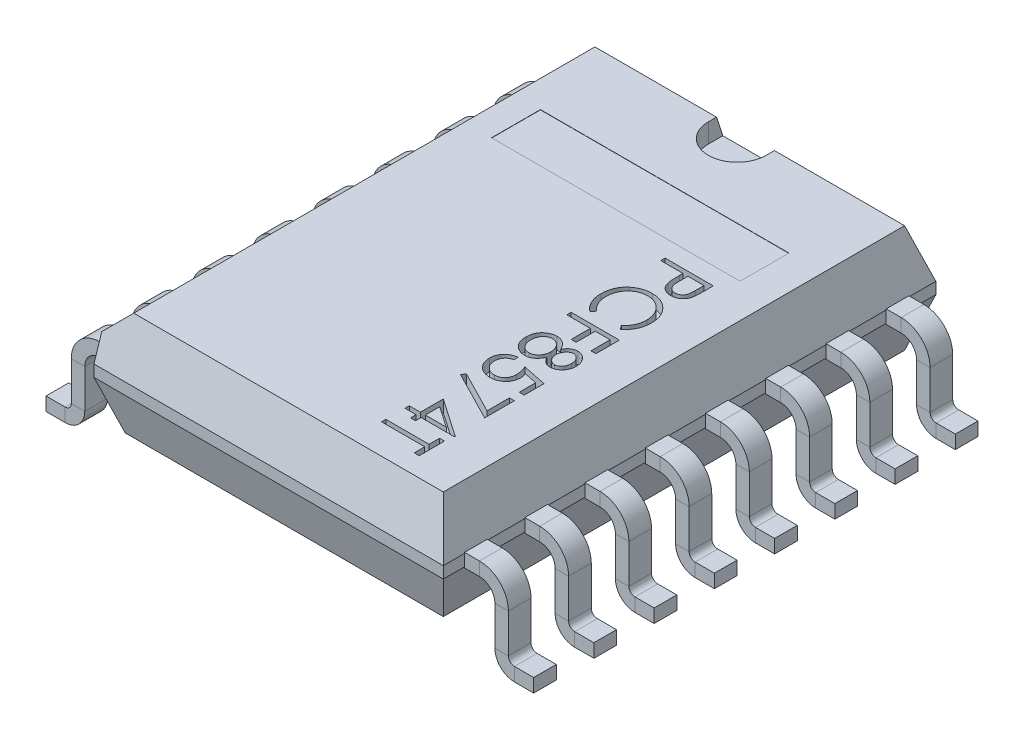
SolidWorks part; units mm, degrees
ref_plane "Front Plane" through (0, 0, 0) normal (0, 0, 1) x (1, 0, 0)
ref_plane "Top Plane" through (0, 0, 0) normal (0, 1, 0) x (1, 0, 0)
ref_plane "Right Plane" through (0, 0, 0) normal (1, 0, 0) x (0, 0, -1)
sketch "Sketch2" plane through (0, 0, 0) normal (0, 1, 0) x (1, 0, 0)
  line L1 (-3.625, 5.11) -> (3.625, 5.11)
  line L2 (-3.625, -5.11) -> (-3.625, 5.11)
  line L6 (-3.625, -5.11) -> (3.625, -5.11)
  line L7 (3.625, -5.11) -> (3.625, 5.11)
  point P6 (0, 5.11)
  point P9 (-3.625, 0)
extrude "Boss-Extrude1" add sketch "Sketch2" along normal blind 0.24
sketch "Sketch9" plane through (0, 0.24, 0) normal (0, 1, 0) x (1, 0, 0)
  line L4 (3.625, -5.11) -> (3.625, 5.11)
  line L5 (3.625, 5.11) -> (-3.625, 5.11)
  line L6 (-3.625, 5.11) -> (-3.625, -5.11)
  line L7 (-3.625, -5.11) -> (3.625, -5.11)
  line L8 (3.625, -5.11) -> (3.625, 5.11)
  line L9 (3.625, 5.11) -> (-3.625, 5.11)
  line L10 (-3.625, 5.11) -> (-3.625, -5.11)
  line L11 (-3.625, -5.11) -> (3.625, -5.11)
  dimension "D1" = 0
extrude "Boss-Extrude3" add sketch "Sketch9" along normal blind 1 separate body
sketch "Sketch10" plane through (0, 0, 0) normal (0, -1, 0) x (1, 0, 0)
  line L4 (3.625, -5.11) -> (3.625, 5.11)
  line L5 (3.625, 5.11) -> (-3.625, 5.11)
  line L6 (-3.625, 5.11) -> (-3.625, -5.11)
  line L7 (-3.625, -5.11) -> (3.625, -5.11)
  line L8 (3.625, -5.11) -> (3.625, 5.11)
  line L9 (3.625, 5.11) -> (-3.625, 5.11)
  line L10 (-3.625, 5.11) -> (-3.625, -5.11)
  line L11 (-3.625, -5.11) -> (3.625, -5.11)
  dimension "D1" = 0
extrude "Boss-Extrude4" add sketch "Sketch10" along normal blind 1 draft 18
sketch "Sketch12" plane through (0, 1.24, 0) normal (0, 1, 0) x (1, 0, 0)
  line L0 (0.601, 4.6135) -> (0.601, 5.4687)
  line L1 (0.601, 5.4687) -> (-0.601, 5.4687)
  line L2 (-0.601, 5.4687) -> (-0.601, 4.6135)
  arc A0 (0.601, 4.6135) -> (-0.601, 4.6135) centre (0, 4.6135) cw
extrude "Cut-Extrude1" cut sketch "Sketch12" against normal blind 0.4
chamfer "Chamfer1" distance 1 angle 18 3 edges at (3.625, 1.24, 0) (0, 1.24, 5.11) (2.113, 1.24, -5.11) first distance on face at (3.625, 0.74, 0) first distance on face at (0, 0.74, 5.11) first distance on face at (0, 0.89, -5.11)
fillet "Chamfer2" radius 0.5 1 edges at (-3.625, 1.24, 0) type face fillet profile chamfer first side face at (-3.625, 0.74, 0) second side face at (-0.0812, 1.24, -2.2745)
sketch "Sketch15" plane through (3.625, 0, 0) normal (1, 0, 0) x (0, 0, -1)
  line L0 (-4.67, 0.26) -> (-4.67, -0.02)
  line L6 (-4.67, 0.26) -> (-4.2, 0.26)
  line L7 (-4.2, 0.26) -> (-4.2, -0.02)
  line L8 (-4.2, -0.02) -> (-4.67, -0.02)
  line L9 (-4.435, 0.26) -> (-4.435, -0.02) construction
ref_plane "Plane2" through (0, -1.5, 0) normal (0, -1, 0) x (-1, 0, 0)
ref_plane "Plane4" through (0, 0, 5.11) normal (0, 0, 1) x (1, 0, 0)
sketch "Sketch24" plane through (0, 0, 5.11) normal (0, 0, 1) x (1, 0, 0)
  line L0 (4.6609, -1.4125) -> (5.0592, -1.4125)
  line L1 (3.625, 0.12) -> (3.9353, 0.12)
  line L2 (3.625, 0.26) -> (3.625, -0.02) construction
  line L4 (4.3949, -0.3396) -> (4.3949, -1.1465)
  arc A0 (3.9353, 0.12) -> (4.3949, -0.3396) centre (3.9353, -0.3396) cw
  arc A1 (4.3949, -1.1465) -> (4.6609, -1.4125) centre (4.6609, -1.1465) ccw
sweep "Sweep1" add profiles "Sketch15" path "Sketch24"
pattern_linear "LPattern1" count 8 spacing 1.25 along (0, 0, -1) of "Sweep1"
mirror "Mirror1" [suppressed] about plane through (0, 0, 0) normal (1, 0, 0) of bodies 108
mirror "Mirror2" about plane through (0, 0, 0) normal (1, 0, 0) of "LPattern1", "Sweep1"
sketch "Sketch33" plane through (0, 1.24, 0) normal (0, 1, 0) x (1, 0, 0)
  line L3 (2.5922, 2.0805) -> (-2.5639, 2.0805)
  line L4 (2.5922, 2.0805) -> (2.5922, 3.0933)
  line L5 (2.5922, 3.0933) -> (-2.5639, 3.0933)
  line L6 (-2.5639, 2.0805) -> (-2.5639, 3.0933)
  point P7 (0.0142, 2.5869)
extrude "Cut-Extrude2" cut sketch "Sketch33" against normal blind 0.005
sketch "Sketch36" plane through (0, 1.24, 0) normal (0, 1, 0) x (1, 0, 0)
  line L0 (1.3981, 1.8468) -> (1.3981, -4.1917) construction
  text T0 "PCF8574T" font "Century Gothic" height 1
extrude "Cut-Extrude3" cut sketch "Sketch36" against normal blind 0.25
equation "\"q\"=0.5"
